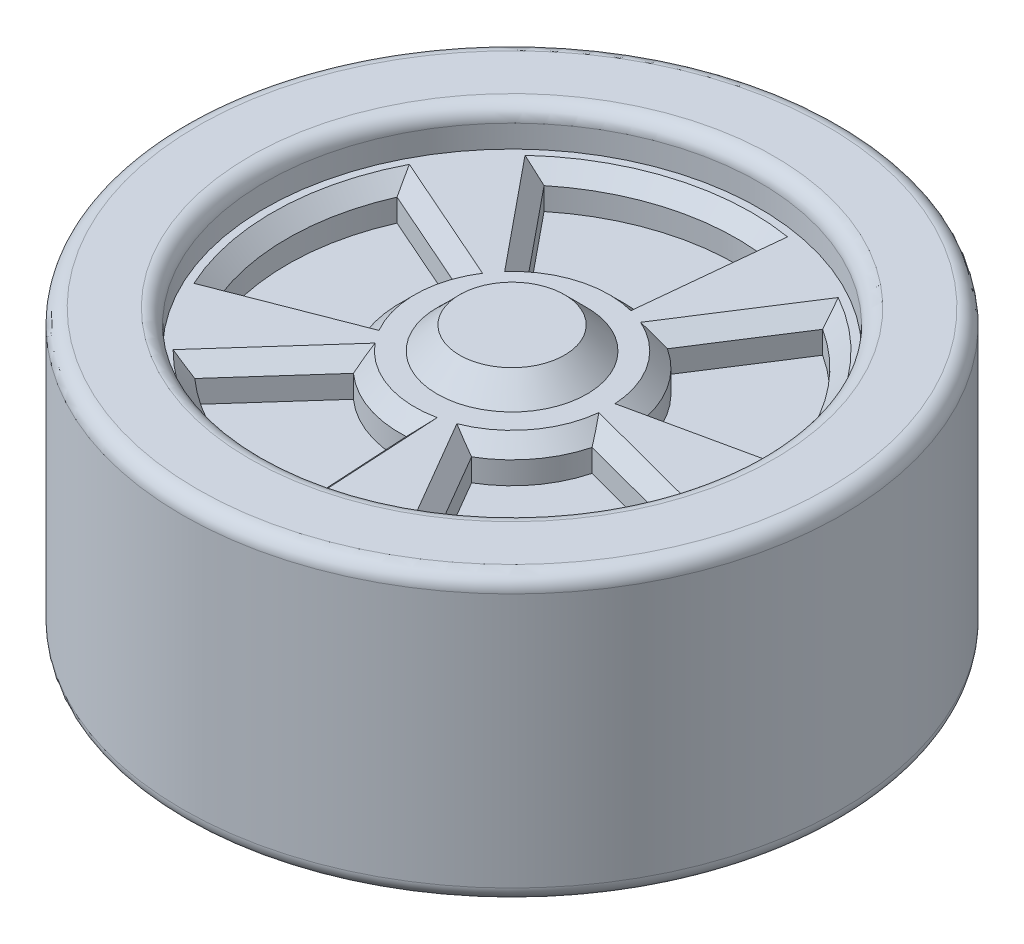
SolidWorks part; units mm, degrees
ref_plane "前视基准面" through (0, 0, 0) normal (0, 0, 1) x (1, 0, 0)
ref_plane "上视基准面" through (0, 0, 0) normal (0, 1, 0) x (1, 0, 0)
ref_plane "右视基准面" through (0, 0, 0) normal (1, 0, 0) x (0, 0, -1)
other "Configuration Table"
sketch "草图1" plane through (0, 0, 0) normal (0, 1, 0) x (1, 0, 0)
  circle A0 centre (0, 0) radius 44
  dimension "D1" = 88
extrude "凸台-拉伸1" add sketch "草图1" along normal blind 38
sketch "草图3" plane through (0, 38, 0) normal (0, 1, 0) x (1, 0, 0)
  circle A0 centre (0, 0) radius 33
  dimension "D1" = 66
extrude "切除-拉伸1" cut sketch "草图3" against normal blind 5
sketch "草图4" plane through (0, 33, 0) normal (0, 1, 0) x (1, 0, 0)
  line L0 (0, 0) -> (-18.9716, 23.2396) construction
  line L1 (0, 0) -> (3.0179, 29.8478) construction
  line L2 (-18.9716, 23.2396) -> (-9.4858, 11.6198)
  line L3 (3.0179, 29.8478) -> (1.5089, 14.9239)
  line L4 (29.3195, 6.3533) -> (14.6598, 3.1767)
  line L5 (16.2396, 25.2245) -> (8.1198, 12.6123)
  line L6 (15.1026, -25.9213) -> (7.5513, -12.9606)
  line L7 (29.0082, -7.65) -> (14.5041, -3.825)
  line L8 (-19.9856, -22.3735) -> (-9.9928, -11.1868)
  line L9 (1.6885, -29.9524) -> (0.8442, -14.9762)
  line L10 (-27.4544, 12.0937) -> (-13.7272, 6.0468)
  line L11 (-27.9647, -10.8617) -> (-13.9823, -5.4308)
  circle A0 centre (0, 0) radius 30 construction
  arc A1 (-9.4858, 11.6198) -> (1.5089, 14.9239) centre (0, 0) cw
  arc A2 (-18.9716, 23.2396) -> (3.0179, 29.8478) centre (0, 0) cw
  arc A3 (8.1198, 12.6123) -> (14.6598, 3.1767) centre (0, 0) cw
  arc A4 (16.2396, 25.2245) -> (29.3195, 6.3533) centre (0, 0) cw
  arc A5 (14.5041, -3.825) -> (7.5513, -12.9606) centre (0, 0) cw
  arc A6 (29.0082, -7.65) -> (15.1026, -25.9213) centre (0, 0) cw
  arc A7 (0.8442, -14.9762) -> (-9.9928, -11.1868) centre (0, 0) cw
  arc A8 (1.6885, -29.9524) -> (-19.9856, -22.3735) centre (0, 0) cw
  arc A9 (-13.9823, -5.4308) -> (-13.7272, 6.0468) centre (0, 0) cw
  arc A10 (-27.9647, -10.8617) -> (-27.4544, 12.0937) centre (0, 0) cw
  point P25 (0, 0)
  dimension "D1" = 60
  dimension "D2" = 45
  dimension "D3" = 5
extrude "切除-拉伸2" cut sketch "草图4" against normal blind 5
sketch "草图5" plane through (0, 33, 0) normal (0, 1, 0) x (1, 0, 0)
  circle A0 centre (0, 0) radius 10
  dimension "D1" = 20
extrude "凸台-拉伸2" add sketch "草图5" along normal blind 3
chamfer "倒角1" distance 3 angle 45 1 edges at (0, 36, 10)
chamfer "倒角2" distance 2 angle 45 20 edges at (11.3269, 33, 19.4409) (11.9363, 33, 9.0843) (21.7562, 33, 5.7375) (23.8726, 33, 18.1686) (1.2664, 33, 22.4643) (-4.9512, 33, 14.1593) (-14.9892, 33, 16.7801) (-9.9023, 33, 28.3186) (-14.9963, 33, -0.3334) (-20.9735, 33, 8.1463) (-20.5908, 33, -9.0702) (-29.9926, 33, -0.6667) (12.3282, 33, -8.5449) (21.9897, 33, -4.765) (12.1797, 33, -18.9184) (24.6564, 33, -17.0898) (-4.3171, 33, -14.3653) (2.2634, 33, -22.3859) (-14.2287, 33, -17.4297) (-8.6341, 33, -28.7307)
fillet "圆角1" radius 2 3 edges at (0, 0, 44) (0, 38, 44) (0, 38, 33)
sketch "草图6" plane through (0, 0, 0) normal (0, -1, 0) x (1, 0, 0)
  circle A0 centre (0, 0) radius 3
  circle A1 centre (0, 0) radius 33
  circle A2 centre (0, 0) radius 7.5
  dimension "D1" = 66
  dimension "D2" = 15
extrude "切除-拉伸3" cut sketch "草图6" against normal blind 2.92 contours A0 | A1 A2 region at (0, 0, 0) region at (-32.0666, 0, 0)
